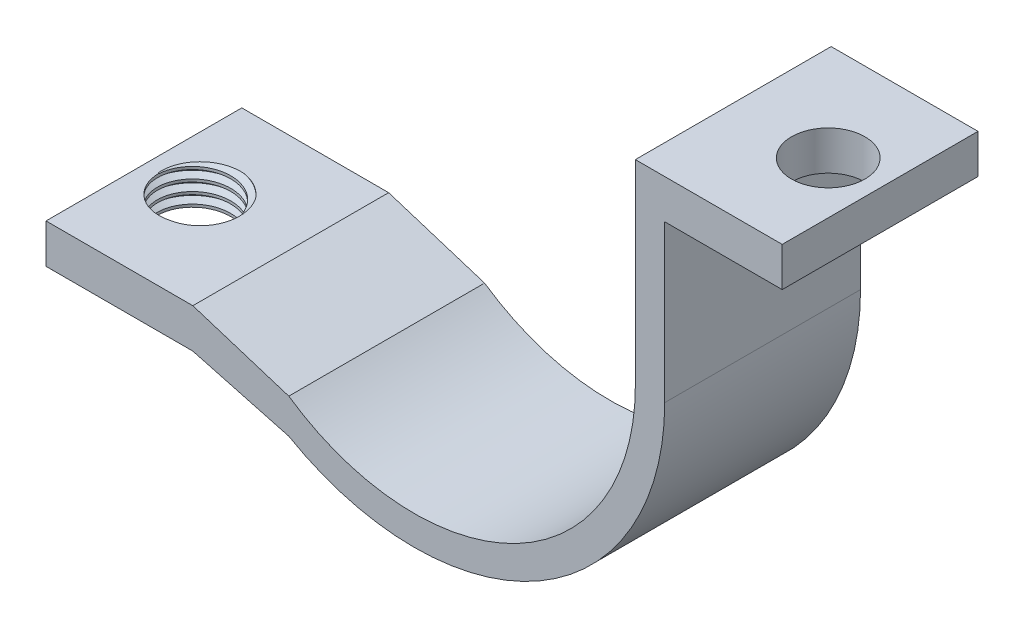
SolidWorks part; units mm, degrees
material "7075-T6, Plate (SS)"
ref_plane "Front Plane" through (0, 0, 0) normal (0, 0, 1) x (1, 0, 0)
ref_plane "Top Plane" through (0, 0, 0) normal (0, 1, 0) x (1, 0, 0)
ref_plane "Right Plane" through (0, 0, 0) normal (1, 0, 0) x (0, 0, -1)
sketch "Sketch5" plane through (0, 0, 0) normal (0, 0, 1) x (1, 0, 0)
  line L1 (28.702, 0) -> (28.702, 25.4)
  line L2 (32.512, 0) -> (32.512, 20.32)
  line L3 (32.512, 25.4) -> (28.702, 25.4)
  line L4 (-28.702, 0) -> (-47.752, 0)
  line L5 (-47.752, 0) -> (-47.752, -5.08)
  line L6 (-47.752, -5.08) -> (-32.1127, -5.08)
  line L7 (-47.752, 0) -> (-47.752, -50000) construction
  line L8 (32.512, 20.32) -> (47.752, 20.32)
  line L10 (32.512, 25.4) -> (47.752, 25.4)
  line L11 (47.752, 20.32) -> (47.752, 25.4)
  line L12 (-28.702, 0) -> (-28.702, -50000) construction
  line L13 (-47.752, -19.7169) -> (0, -32.512) construction
  line L14 (0, -32.512) -> (-50000, -32.512) construction
  line L15 (-47.752, -19.7169) -> (-28.702, -19.7169)
  line L16 (-47.752, -19.7169) -> (-47.752, -24.8213)
  line L17 (-47.752, -24.8213) -> (-28.702, -24.8213)
  line L18 (-28.702, -24.8213) -> (-16.256, -28.1562)
  line L19 (-28.702, -19.7169) -> (-16.256, -23.6548)
  arc A0 (-28.702, 0) -> (28.702, 0) centre (0, 0) ccw construction
  arc A1 (-32.1127, -5.08) -> (32.512, 0) centre (0, 0) ccw construction
  arc A2 (-16.256, -28.1562) -> (32.512, 0) centre (0, 0) ccw
  arc A3 (-16.256, -23.6548) -> (28.702, 0) centre (0, 0) ccw
  point P5 (0, -32.512)
  point P8 (0, 32.512)
  point P12 (32.512, 20.32)
  point P16 (-47.752, -19.7169)
  dimension "D1" = 32.512
  dimension "D2" = 3.81
  dimension "D6" = 57.912
  dimension "D3" = 5.08
  dimension "D4" = 19.05
  dimension "D5" = 3.81
  dimension "D7" = 5.08
  dimension "D8" = 19.05
  dimension "D9" = 15
  dimension "D10" = 5.1044
  dimension "D11" = 19.05
  dimension "D12" = 4.5015
extrude "Boss-Extrude3" add sketch "Sketch5" along normal blind 25.4 contours L19 A3 L1 L3 L10 L11 L8 L2 A2 L18 L17 L16 L15
sketch "Sketch7" plane through (0, 25.4, 0) normal (0, 1, 0) x (1, 0, 0)
  line L0 (-47.752, -12.7) -> (47.752, -12.7) construction
  line L2 (47.752, -25.4) -> (47.752, 0) construction
  circle A0 centre (-41.021, -12.7) radius 4.7625
  circle A1 centre (41.021, -12.7) radius 4.7625
  point P2 (0, 0)
  point P3 (-47.752, -12.7)
  point P6 (-41.021, -12.7)
  point P7 (41.021, -12.7)
  point P8 (0, -12.7)
  point P13 (0, 0)
  dimension "D3" = 9.525
  dimension "D1" = 82.042
  dimension "D2" = 41.021
  dimension "D4" = 95.504
  dimension "D5" = 6.731
extrude "Cut-Extrude1" cut sketch "Sketch7" against normal blind 54.102
thread "Thread1" pitch 1.4111 method cut profile "Thread Profile1" start angle 0, offset 1, length 0, pitch 1.4111, diameter 9.525
ref_plane "Plane1" through (-45.7835, -18.7169, 12.7) normal (0, 0, 1) x (-1, 0, 0)
sketch "Thread Profile1" plane through (-45.7835, -18.7169, 12.7) normal (0, 0, 1) x (-1, 0, 0)
  line L0 (0, 0) -> (0, 1.4111) construction
  line L1 (0, 0) -> (0.7638, 0.441)
  line L2 (0.7638, 0.441) -> (0.7638, 0.6174)
  line L3 (0.7638, 0.6174) -> (0, 1.0583)
  line L4 (0.7638, 0.5292) -> (0, 0.5292) construction
  line L11 (0, 0) -> (0, 1.0583)
  point P2 (0, 0)
  dimension "Pitch" = 1.4111
  dimension "Profile_Angle" = 60
  dimension "Profile_Land" = 0.1764
  dimension "Profile_Height" = 0.7638
